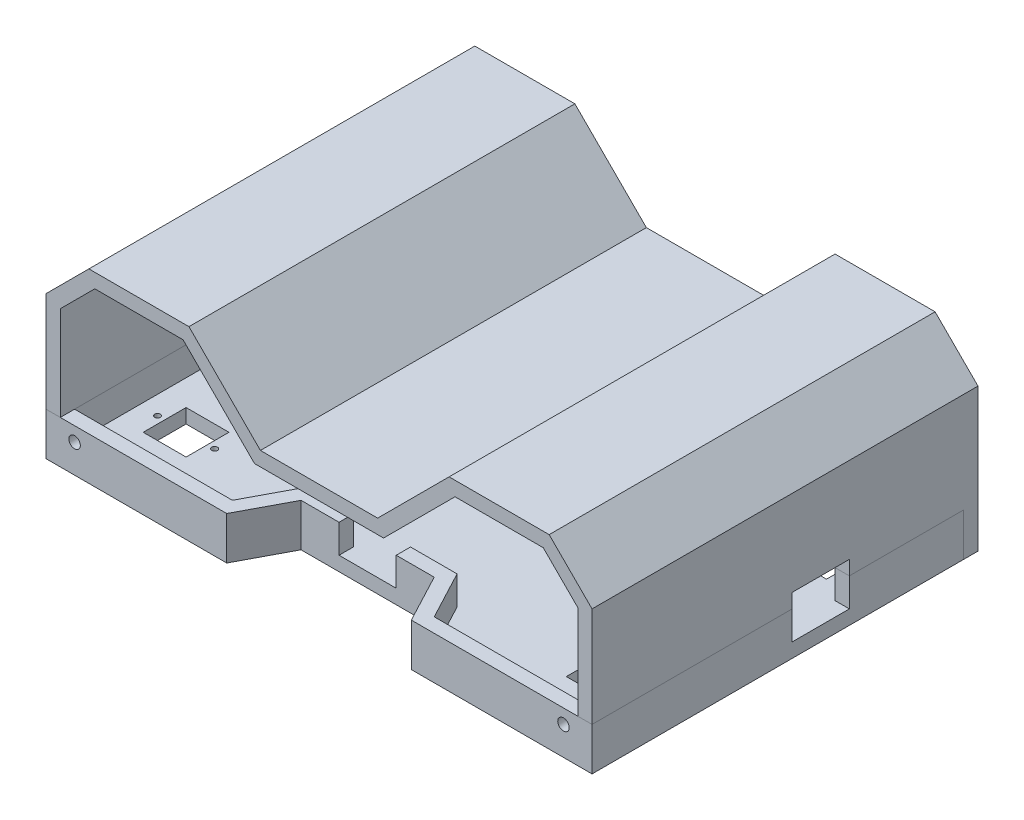
SolidWorks part; units mm, degrees
ref_plane "Front Plane" through (0, 0, 0) normal (0, 0, 1) x (1, 0, 0)
ref_plane "Top Plane" through (0, 0, 0) normal (0, 1, 0) x (1, 0, 0)
ref_plane "Right Plane" through (0, 0, 0) normal (1, 0, 0) x (0, 0, -1)
sketch "Sketch1" plane through (0, 0, 0) normal (0, 1, 0) x (1, 0, 0)
  line L0 (-36.5, -58) -> (-27.5, -41)
  line L1 (-88.5, 58) -> (88.5, 58)
  line L2 (-88.5, 58) -> (-88.5, -58)
  line L3 (-88.5, -58) -> (88.5, -58)
  line L4 (88.5, 58) -> (88.5, -58)
  line L5 (-27.5, -41) -> (27.5, -41)
  line L6 (27.5, -41) -> (36.5, -58)
  line L8 (-36.5, -58) -> (36.5, -58)
  line L9 (0, -63.8) -> (0, 63.8) construction
  line L10 (-97.35, 0) -> (97.35, 0) construction
  circle A0 centre (-84, 53.5) radius 1.5
  circle A1 centre (84, 53.5) radius 1.5
  circle A2 centre (-84, -53.5) radius 1.5
  circle A3 centre (84, -53.5) radius 1.5
  point P4 (0, 58)
  point P6 (88.5, 0)
  point P12 (0, -41)
  point P13 (0, -58)
  dimension "D7" = 3
  dimension "D1" = 116
  dimension "D2" = 177
  dimension "D3" = 73
  dimension "D4" = 55
  dimension "D5" = 17
  dimension "D8" = 4.5
  dimension "D9" = 4.5
sketch "Sketch3" plane through (0, 0, 0) normal (0, 1, 0) x (1, 0, 0)
  line L8 (95.5, 65) -> (-95.5, 65)
  line L9 (95.5, -65) -> (95.5, 65)
  line L10 (-95.5, -65) -> (95.5, -65)
  line L11 (-95.5, 65) -> (-95.5, -65)
  line L12 (95.5, 65) -> (-95.5, 65)
  line L13 (95.5, -65) -> (95.5, 65)
  line L14 (-95.5, -65) -> (-32.2854, -65)
  line L15 (-95.5, 65) -> (-95.5, -65)
  line L17 (32.2854, -65) -> (95.5, -65)
  line L20 (-30.3135, -61.2752) -> (-23.2854, -48)
  line L21 (23.2854, -48) -> (30.3135, -61.2752)
  line L22 (-23.2854, -48) -> (23.2854, -48)
  line L23 (-32.2854, -65) -> (-23.2854, -48)
  line L24 (23.2854, -48) -> (32.2854, -65)
  line L25 (-23.2854, -48) -> (23.2854, -48)
  point P0 (-33.4922, -63)
  dimension "D1" = 7
  dimension "D2" = 7
extrude "Boss-Extrude2" add sketch "Sketch3" along normal blind 15
shell "Shell1" thickness 5 removed face at (0, 15, 28.25)
sketch "Sketch4" plane through (0, 0, 0) normal (0, 1, 0) x (1, 0, 0)
  line L0 (-88.5, -58) -> (88.5, -58) construction
  line L1 (-5, 21) -> (5, 21)
  line L2 (-5, 21) -> (-5, 9)
  line L3 (-5, 9) -> (5, 9)
  line L4 (5, 21) -> (5, 9)
  line L5 (90.5, -60) -> (90.5, 60) construction
  line L6 (54.5, 7) -> (81.5, 7)
  line L7 (54.5, 7) -> (54.5, -13)
  line L8 (54.5, -13) -> (81.5, -13)
  line L9 (81.5, 7) -> (81.5, -13)
  line L10 (90.5, -60) -> (90.5, 60) construction
  line L11 (66.5, -30) -> (81.5, -30)
  line L12 (66.5, -30) -> (66.5, -45)
  line L13 (66.5, -45) -> (81.5, -45)
  line L14 (81.5, -30) -> (81.5, -45)
  line L15 (0, -8.25) -> (0, 8.25) construction
  line L16 (-66.5, -30) -> (-66.5, -45)
  line L17 (-66.5, -45) -> (-81.5, -45)
  line L18 (-81.5, -30) -> (-81.5, -45)
  line L19 (-66.5, -30) -> (-81.5, -30)
  line L20 (-84, -37.5) -> (-64, -37.5) construction
  line L21 (90.5, 60) -> (-90.5, 60) construction
  line L22 (42.5, 45) -> (82.5, 45)
  line L23 (42.5, 45) -> (42.5, 30)
  line L24 (42.5, 30) -> (82.5, 30)
  line L25 (82.5, 45) -> (82.5, 30)
  circle A0 centre (-84, -37.5) radius 1
  circle A1 centre (-64, -37.5) radius 1
  point P6 (0, 9)
  point P28 (-74, -37.5)
  point P29 (-81.5, -37.5)
  point P30 (-74, -30)
  dimension "D10" = 2
  dimension "D1" = 67
  dimension "D2" = 12
  dimension "D3" = 10
  dimension "D4" = 65
  dimension "D5" = 20
  dimension "D6" = 9
  dimension "D7" = 27
  dimension "D8" = 13
  dimension "D9" = 15
  dimension "D11" = 20
  dimension "D12" = 15
  dimension "D13" = 40
  dimension "D14" = 8
  dimension "D15" = 15
extrude "Cut-Extrude2" cut sketch "Sketch4" against normal through all and the other way through all
sketch "Sketch5" plane through (0, 0, 0) normal (0, 1, 0) x (1, 0, 0)
  line L0 (0, -8.25) -> (0, 8.25) construction
  line L1 (-85.5, 55) -> (-82.5, 55)
  line L2 (-85.5, 55) -> (-85.5, 52)
  line L3 (-85.5, 52) -> (-82.5, 52)
  line L4 (-82.5, 55) -> (-82.5, 52)
  line L5 (82.5, 55) -> (82.5, 52)
  line L6 (85.5, 52) -> (82.5, 52)
  line L7 (85.5, 55) -> (85.5, 52)
  line L8 (85.5, 55) -> (82.5, 55)
  line L9 (-8.25, 0) -> (8.25, 0) construction
  line L10 (85.5, -55) -> (82.5, -55)
  line L11 (85.5, -55) -> (85.5, -52)
  line L12 (85.5, -52) -> (82.5, -52)
  line L13 (82.5, -55) -> (82.5, -52)
  line L14 (-82.5, -55) -> (-82.5, -52)
  line L15 (-85.5, -52) -> (-82.5, -52)
  line L16 (-85.5, -55) -> (-85.5, -52)
  line L17 (-85.5, -55) -> (-82.5, -55)
  circle A0 centre (-84, 53.5) radius 1.5 construction
extrude "Cut-Extrude4" cut sketch "Sketch5" along normal through all
sketch "Sketch6" plane through (0, 0, -65) normal (0, 0, -1) x (-1, 0, 0)
  line L0 (95.5, 15) -> (95.5, 0) construction
  line L2 (-95.5, 50) -> (-95.5, 0)
  line L3 (-95.5, 0) -> (95.5, 0)
  line L4 (95.5, 50) -> (95.5, 0)
  line L5 (-95.5, 15) -> (-95.5, 0) construction
  line L6 (-80.5, 65) -> (-45.5, 65)
  line L7 (-45.5, 65) -> (-20.5, 40)
  line L8 (-20.5, 40) -> (20.5, 40)
  line L9 (20.5, 40) -> (45.5, 65)
  line L10 (45.5, 65) -> (80.5, 65)
  line L11 (-95.5, 50) -> (-80.5, 65)
  line L12 (80.5, 65) -> (95.5, 50)
  circle A1 centre (-80.5, 30) radius 2
  circle A2 centre (-45.5, 30) radius 2
  point P14 (-95.5, 65)
  point P18 (95.5, 65)
  point P19 (0, 40)
  point P22 (0, 0)
  dimension "D1" = 35
  dimension "D2" = 4
  dimension "D3" = 30
  dimension "D4" = 15
  dimension "D5" = 65
  dimension "D6" = 40
  dimension "D7" = 50
extrude "Boss-Extrude3" add sketch "Sketch6" along normal blind 5 separate body
sketch "Sketch7" plane through (0, 0, -70) normal (0, 0, -1) x (-1, 0, 0)
  line L0 (-95.5, 0) -> (95.5, 0) construction
  line L1 (0, 8.25) -> (0, -8.25) construction
  circle A0 centre (-85.5, 10) radius 2
  circle A1 centre (85.5, 10) radius 2
  point P2 (0, 0)
  dimension "D1" = 4
  dimension "D2" = 10
  dimension "D3" = 10
extrude "Cut-Extrude5" cut sketch "Sketch7" against normal through all and the other way through all
sketch "Sketch8" plane through (0, 0, -65) normal (0, 0, 1) x (1, 0, 0)
  line L71 (45.5, 65) -> (20.5, 40) construction
  line L72 (80.5, 65) -> (45.5, 65) construction
  line L73 (95.5, 50) -> (80.5, 65) construction
  line L74 (95.5, 50) -> (95.5, 0) construction
  line L75 (45.5, 65) -> (20.5, 40)
  line L76 (80.5, 65) -> (45.5, 65)
  line L77 (95.5, 50) -> (80.5, 65)
  line L78 (95.5, 50) -> (95.5, 15)
  line L79 (90.5, 15) -> (95.5, 15)
  line L80 (-90.5, 0) -> (-90.5, 47.9289)
  line L81 (-90.5, 47.9289) -> (-78.4289, 60)
  line L82 (-78.4289, 60) -> (-47.5711, 60)
  line L83 (-47.5711, 60) -> (-22.5711, 35)
  line L84 (-22.5711, 35) -> (22.5711, 35)
  line L85 (22.5711, 35) -> (47.5711, 60)
  line L86 (47.5711, 60) -> (78.4289, 60)
  line L87 (78.4289, 60) -> (90.5, 47.9289)
  line L88 (90.5, 47.9289) -> (90.5, 0)
  line L89 (-90.5, 15) -> (-90.5, 47.9289)
  line L90 (-90.5, 47.9289) -> (-78.4289, 60)
  line L91 (-78.4289, 60) -> (-47.5711, 60)
  line L92 (-47.5711, 60) -> (-22.5711, 35)
  line L93 (-22.5711, 35) -> (22.5711, 35)
  line L94 (22.5711, 35) -> (47.5711, 60)
  line L95 (47.5711, 60) -> (78.4289, 60)
  line L96 (78.4289, 60) -> (90.5, 47.9289)
  line L97 (90.5, 47.9289) -> (90.5, 15)
  line L98 (32.2854, 15) -> (95.5, 15) construction
  line L99 (-95.5, 15) -> (-90.5, 15)
  line L100 (-95.5, 50) -> (-95.5, 0) construction
  line L101 (-80.5, 65) -> (-95.5, 50) construction
  line L102 (-45.5, 65) -> (-80.5, 65) construction
  line L103 (-20.5, 40) -> (-45.5, 65) construction
  line L104 (20.5, 40) -> (-20.5, 40) construction
  line L105 (-95.5, 50) -> (-95.5, 15)
  line L106 (-80.5, 65) -> (-95.5, 50)
  line L107 (-45.5, 65) -> (-80.5, 65)
  line L108 (-20.5, 40) -> (-45.5, 65)
  line L109 (20.5, 40) -> (-20.5, 40)
  dimension "D1" = 5
extrude "Boss-Extrude4" add sketch "Sketch8" along normal up to surface (130 mm away) up to face at (83.5, 10, 65)
sketch "Sketch9" plane through (0, 0, -65) normal (0, 0, 1) x (1, 0, 0)
  line L0 (80.5, 30) -> (45.5, 30) construction
  circle A0 centre (63, 38) radius 10
  circle A1 centre (63, 38) radius 2.5
  point P2 (63, 30)
  dimension "D2" = 20
  dimension "D3" = 5
  dimension "D1" = 8
extrude "Boss-Extrude5" [suppressed] add sketch "Sketch9" along normal blind 20 from offset 38 separate body
chamfer "Chamfer2" distance 3 angle 45 4 edges at (0, 0, -21) (5, 0, -15) (0, 0, -9) (-5, 0, -15)
sketch "Sketch10" plane through (0, 0, 0) normal (0, -1, 0) x (1, 0, 0)
  line L0 (11.5, -3.5) -> (11.5, -26.5) construction
  line L1 (5, -21) -> (5, -9) construction
  line L2 (0, -8.25) -> (0, 8.25) construction
  line L4 (-15, 0) -> (15, 0) construction
  line L5 (-15, 0) -> (-15, -30) construction
  line L6 (-15, -30) -> (15, -30) construction
  line L7 (15, 0) -> (15, -30) construction
  circle A0 centre (11.5, -3.5) radius 1.5
  circle A1 centre (11.5, -26.5) radius 1.5
  circle A2 centre (-11.5, -26.5) radius 1.5
  circle A3 centre (-11.5, -3.5) radius 1.5
  point P7 (5, -15)
  point P8 (11.5, -15)
  point P10 (0, 0)
  dimension "D1" = 3
  dimension "D2" = 3.5
  dimension "D4" = 30
  dimension "D5" = 30
  dimension "D6" = 3.5
  dimension "D7" = 3.5
extrude "Cut-Extrude6" cut sketch "Sketch10" against normal blind 5
sketch "Sketch11" plane through (0, 0, 48) normal (0, 0, 1) x (1, 0, 0)
  line L0 (-23.2854, 15) -> (23.2854, 15) construction
  line L1 (-10, 15) -> (10, 15)
  line L2 (-10, 15) -> (-10, 5)
  line L3 (-10, 5) -> (10, 5)
  line L4 (10, 15) -> (10, 5)
  point P6 (0, 15)
  dimension "D1" = 10
  dimension "D2" = 20
extrude "Cut-Extrude7" cut sketch "Sketch11" against normal blind 5 contours L2 L3 L4 L1
sketch "Sketch12" plane through (95.5, 0, 0) normal (1, 0, 0) x (0, 0, -1)
  line L1 (5, 20) -> (25, 20)
  line L2 (5, 20) -> (5, 5)
  line L3 (5, 5) -> (25, 5)
  line L4 (25, 20) -> (25, 5)
  line L5 (21, 0) -> (9, 0) construction
  line L6 (21, 0) -> (9, 0) construction
  point P4 (15, 0)
  point P5 (15, 5)
  dimension "D1" = 20
  dimension "D2" = 15
  dimension "D3" = 5
extrude "Cut-Extrude8" cut sketch "Sketch12" against normal blind 6
fillet "Fillet1" radius 3 1 edges at (90.5, 20, -15)
